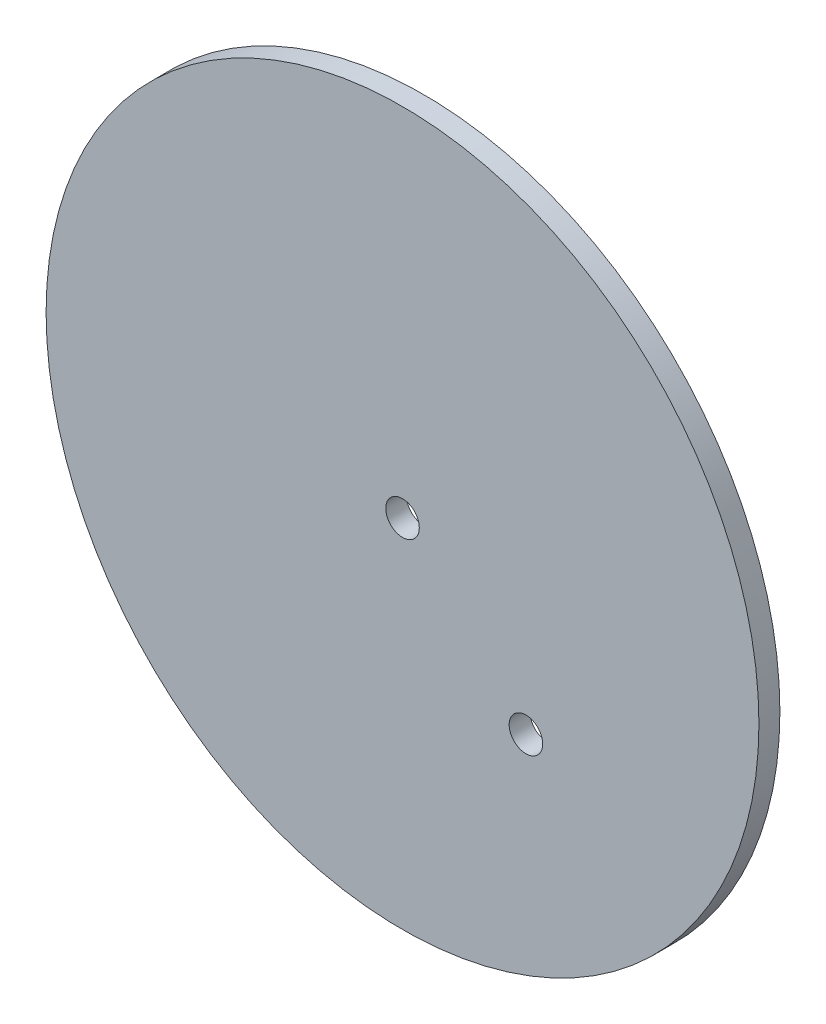
SolidWorks part; units mm, degrees
ref_plane "Front Plane" through (0, 0, 0) normal (0, 0, 1) x (1, 0, 0)
ref_plane "Top Plane" through (0, 0, 0) normal (0, 1, 0) x (1, 0, 0)
ref_plane "Right Plane" through (0, 0, 0) normal (1, 0, 0) x (0, 0, -1)
sketch "Sketch1" plane through (0, 0, 0) normal (0, 0, 1) x (1, 0, 0)
  circle A0 centre (0, 0) radius 42.5
  circle A1 centre (0, 0) radius 2
  circle A2 centre (0, 0) radius 18 construction
  circle A3 centre (0, 0) radius 36 construction
  circle A5 centre (0, -27) radius 9 construction
  circle A6 centre (0, -27) radius 2 construction
  circle A7 centre (0, 0) radius 14 construction
  circle A8 centre (14.7158, -14.9815) radius 10 construction
  circle A9 centre (14.7158, -14.9815) radius 7 construction
  circle A10 centre (14.7158, -14.9815) radius 2
  dimension "D1" = 4
  dimension "D2" = 85
  dimension "D3" = 36
  dimension "D4" = 72
  dimension "D5" = 4
  dimension "D6" = 28
  dimension "D7" = 20
  dimension "D8" = 14
  dimension "D9" = 4
extrude "Boss-Extrude1" add sketch "Sketch1" along normal blind 1.25 and the other way blind 1.25 contours A0 A1 region at (-41.2979, 0, 0)
